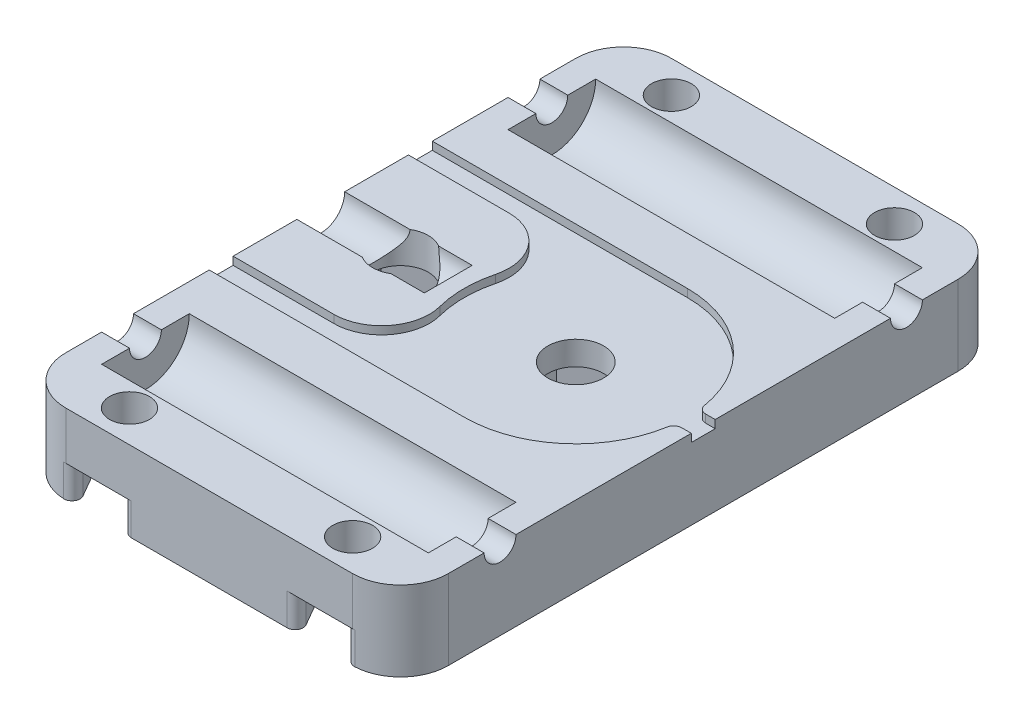
SolidWorks part; units mm, degrees
ref_plane "Спереди" through (0, 0, 0) normal (0, 0, 1) x (1, 0, 0)
ref_plane "Сверху" through (0, 0, 0) normal (0, 1, 0) x (1, 0, 0)
ref_plane "Справа" through (0, 0, 0) normal (1, 0, 0) x (0, 0, -1)
sketch "Эскиз1" plane through (0, 0, 0) normal (0, 1, 0) x (1, 0, 0)
  line L1 (-12, 19) -> (12, 19)
  line L2 (-12, 19) -> (-12, -19)
  line L3 (-12, -19) -> (12, -19)
  line L4 (12, 19) -> (12, -19)
  line L5 (-12, 19) -> (12, -19) construction
  line L6 (-12, -19) -> (12, 19) construction
  point P0 (0, 0)
  dimension "D1" = 38
  dimension "D2" = 24
extrude "Бобышка-Вытянуть1" add sketch "Эскиз1" along normal blind 5
sketch "Эскиз2" plane through (0, 0, 0) normal (1, 0, 0) x (0, 0, -1)
  line L0 (-19, 5) -> (19, 5) construction
  line L1 (0, 0) -> (0, 19.0603) construction
  line L2 (-10, 5) -> (10, 5) construction
  circle A0 centre (-12.75, 5) radius 2.75
  circle A1 centre (12.75, 5) radius 2.75
  dimension "D1" = 5.5
  dimension "D2" = 20
extrude "Вырез-Вытянуть1" cut sketch "Эскиз2" against normal mid plane 20.5
sketch "Эскиз3" plane through (0, 0, 0) normal (1, 0, 0) x (0, 0, -1)
  circle A0 centre (-12.75, 5) radius 1
  circle A1 centre (12.75, 5) radius 1
  arc A2 (10, 5) -> (15.5, 5) centre (12.75, 5) ccw construction
  arc A3 (-15.5, 5) -> (-10, 5) centre (-12.75, 5) ccw construction
  dimension "D1" = 2
  dimension "D2" = 2
extrude "Вырез-Вытянуть2" cut sketch "Эскиз3" against normal through all both and the other way through all
sketch "Эскиз4" plane through (0, 5, 0) normal (0, 1, 0) x (1, 0, 0)
  line L0 (12, -11.75) -> (12, 11.75) construction
  line L1 (4, 7) -> (-12, 7)
  line L2 (-12, 11.75) -> (-12, -11.75) construction
  line L3 (-12, 7) -> (-12, 5.5)
  line L4 (-12, 5.5) -> (-0.3301, 5.5)
  line L5 (10.9597, 0.75) -> (12, 0.75)
  line L6 (12, 0.75) -> (12, -0.75)
  line L7 (12, -0.75) -> (10.9597, -0.75)
  line L8 (11, 0) -> (12, 0) construction
  line L9 (4, 0) -> (-12, 0) construction
  line L10 (-12, -7) -> (-12, -5.5)
  line L11 (-12, -5.5) -> (-0.3301, -5.5)
  line L12 (4, -7) -> (-12, -7)
  arc A0 (-0.3301, 5.5) -> (-0.3301, -5.5) centre (4, 0) ccw
  arc A1 (4, 7) -> (-0.3301, 5.5) centre (4, 0) ccw construction
  arc A2 (10.9597, 0.75) -> (4, 7) centre (4, 0) ccw
  arc A3 (11, 0) -> (10.9597, 0.75) centre (4, 0) ccw construction
  arc A4 (10.9597, -0.75) -> (11, 0) centre (4, 0) ccw construction
  arc A5 (4, -7) -> (10.9597, -0.75) centre (4, 0) ccw
  arc A6 (-0.3301, -5.5) -> (4, -7) centre (4, 0) ccw construction
  dimension "D2" = 14
  dimension "D1" = 8
  dimension "D3" = 1.5
  dimension "D4" = 1.5
extrude "Вырез-Вытянуть3" cut sketch "Эскиз4" against normal blind 0.5
sketch "Эскиз5" plane through (0, 5, 0) normal (0, 1, 0) x (1, 0, 0)
  line L0 (-12, 5.5) -> (-12, -5.5) construction
  circle A0 centre (4, 0) radius 1.75
  circle A1 centre (-7, 0) radius 1.75
  point P5 (0, 0)
  dimension "D1" = 3.5
  dimension "D2" = 3.5
  dimension "D3" = 5
extrude "Вырез-Вытянуть4" cut sketch "Эскиз5" against normal through all
fillet "Скругление1" radius 3 2 edges at (-0.3301, 4.75, 5.5) (-0.3301, 4.75, -5.5)
fillet "Скругление2" radius 3 4 edges at (-12, 2.5, -19) (12, 2.5, -19) (-12, 2.5, 19) (12, 2.5, 19)
sketch "Эскиз6" plane through (-12, 0, 0) normal (-1, 0, 0) x (0, 0, 1)
  line L0 (-5.5, 5) -> (5.5, 5) construction
  circle A0 centre (0, 5) radius 1.5
  dimension "D1" = 3
extrude "Вырез-Вытянуть5" cut sketch "Эскиз6" against normal blind 8
fillet "Скругление3" radius 0.5 2 edges at (10.9597, 4.75, 0.75) (10.9597, 4.75, -0.75)
sketch "Эскиз7" plane through (0, 5, 0) normal (0, 1, 0) x (1, 0, 0)
  line L0 (-9, -19) -> (9, -19) construction
  line L1 (7, 17) -> (-7, 17) construction
  line L2 (7, 17) -> (7, -17) construction
  line L3 (7, -17) -> (-7, -17) construction
  line L4 (-7, 17) -> (-7, -17) construction
  line L5 (7, 17) -> (-7, -17) construction
  line L6 (7, -17) -> (-7, 17) construction
  circle A0 centre (-7, 17) radius 1.25
  circle A1 centre (7, 17) radius 1.25
  circle A2 centre (7, -17) radius 1.25
  circle A3 centre (-7, -17) radius 1.25
  point P0 (0, 0)
  dimension "D1" = 2
  dimension "D2" = 14
  dimension "D3" = 2.5
  dimension "D4" = 2.5
  dimension "D5" = 2.5
  dimension "D6" = 2.5
extrude "Вырез-Вытянуть6" cut sketch "Эскиз7" against normal through all
sketch "Эскиз9" plane through (0, 0, 0) normal (0, -1, 0) x (1, 0, 0)
  line L1 (-7, 3.2909) -> (-9.85, 1.6454)
  line L2 (-9.85, 1.6454) -> (-9.85, -1.6454)
  line L3 (-9.85, -1.6454) -> (-7, -3.2909)
  line L4 (-7, -3.2909) -> (-4.15, -1.6454)
  line L5 (-4.15, -1.6454) -> (-4.15, 1.6454)
  line L6 (-4.15, 1.6454) -> (-7, 3.2909)
  line L7 (6.85, -1.6454) -> (6.85, 1.6454)
  line L8 (6.85, 1.6454) -> (4, 3.2909)
  line L9 (4, 3.2909) -> (1.15, 1.6454)
  line L10 (1.15, 1.6454) -> (1.15, -1.6454)
  line L11 (1.15, -1.6454) -> (4, -3.2909)
  line L12 (4, -3.2909) -> (6.85, -1.6454)
  circle A0 centre (-7, 0) radius 2.85 construction
  circle A1 centre (4, 0) radius 2.85 construction
  dimension "D1" = 5.7
  dimension "D2" = 5.7
extrude "Вырез-Вытянуть9" cut sketch "Эскиз9" against normal blind 3
sketch "Эскиз10" plane through (0, 0, 0) normal (0, -1, 0) x (1, 0, 0)
  line L0 (0, 19) -> (0, -19) construction
  line L1 (-9, 19) -> (9, 19) construction
  line L2 (9, -19) -> (-9, -19) construction
  line L3 (0, 0) -> (12, 0) construction
  line L4 (12, 16) -> (12, -16) construction
  line L5 (8.198, 14.925) -> (5.802, 14.925)
  line L6 (-5.802, 14.925) -> (-4.604, 17)
  line L7 (-4.604, 17) -> (-5.802, 19.075)
  line L8 (-5.802, 19.075) -> (-8.198, 19.075)
  line L9 (-8.198, 19.075) -> (-9.396, 17)
  line L10 (-9.396, 17) -> (-8.198, 14.925)
  line L11 (-8.198, 14.925) -> (-5.802, 14.925)
  line L18 (9.396, 17) -> (8.198, 14.925)
  line L19 (8.198, 19.075) -> (9.396, 17)
  line L20 (5.802, 19.075) -> (8.198, 19.075)
  line L21 (4.604, 17) -> (5.802, 19.075)
  line L22 (5.802, 14.925) -> (4.604, 17)
  line L23 (9.396, -17) -> (8.198, -14.925)
  line L24 (8.198, -19.075) -> (9.396, -17)
  line L25 (5.802, -19.075) -> (8.198, -19.075)
  line L26 (4.604, -17) -> (5.802, -19.075)
  line L27 (5.802, -14.925) -> (4.604, -17)
  line L28 (8.198, -14.925) -> (5.802, -14.925)
  line L29 (-8.198, -14.925) -> (-5.802, -14.925)
  line L30 (-9.396, -17) -> (-8.198, -14.925)
  line L31 (-8.198, -19.075) -> (-9.396, -17)
  line L32 (-5.802, -19.075) -> (-8.198, -19.075)
  line L33 (-4.604, -17) -> (-5.802, -19.075)
  line L34 (-5.802, -14.925) -> (-4.604, -17)
  circle A0 centre (-7, 17) radius 2.075 construction
  dimension "D1" = 4.15
extrude "Вырез-Вытянуть10" cut sketch "Эскиз10" against normal blind 2
fillet "Скругление4" radius 0.5 8 edges at (-8.2413, 1, -19) (-5.7587, 1, -19) (5.7587, 1, -19) (8.2413, 1, -19) (8.2413, 1, 19) (5.7587, 1, 19) (-5.7587, 1, 19) (-8.2413, 1, 19)
equation "\"Ball_bearing_D\"= 12.7"
equation "\"Ball_bearing_h1\"= 9"
equation "\"Ball_bearing_d1\"= 5.9"
equation "\"Ball_bearing_d2\"= 18"
equation "\"Ball_bearing_h2\"= 6.6"
equation "\"Brake_tube_d1\"= 2"
equation "\"Brake_tube_d2\"= 5"
equation "\"Brake_tube_h\"= 20"
equation "\"print_offset\"= 0.5"
equation "\"D1@Эскиз2\"=\"print_offset\"+\"Brake_tube_d2\""
equation "\"D1@Вырез-Вытянуть1\"=\"Brake_tube_h\"+\"print_offset\""
equation "\"D1@Эскиз3\"=\"Brake_tube_d1\""
equation "\"D2@Эскиз3\"=\"D1@Эскиз3\""
equation "\"inner_distance\"=20"
equation "\"D2@Эскиз2\"=\"inner_distance\""
equation "\"D1@Эскиз1\"=\"inner_distance\"+\"Brake_tube_d2\"*2+8"
equation "\"D4@Эскиз4\"=\"D3@Эскиз4\""
equation "\"D1@Эскиз5\"=\"print_offset\"+3"
equation "\"D2@Эскиз5\"=\"D1@Эскиз5\""
equation "\"D2@Эскиз1\"=\"Brake_tube_h\"+4"
equation "\"D4@Эскиз7\"=\"D3@Эскиз7\""
equation "\"D5@Эскиз7\"=\"D3@Эскиз7\""
equation "\"D6@Эскиз7\"=\"D3@Эскиз7\""
equation "\"D1@Эскиз9\"=\"print_offset\"/2+5.45"
equation "\"D2@Эскиз9\"=\"D1@Эскиз9\""
